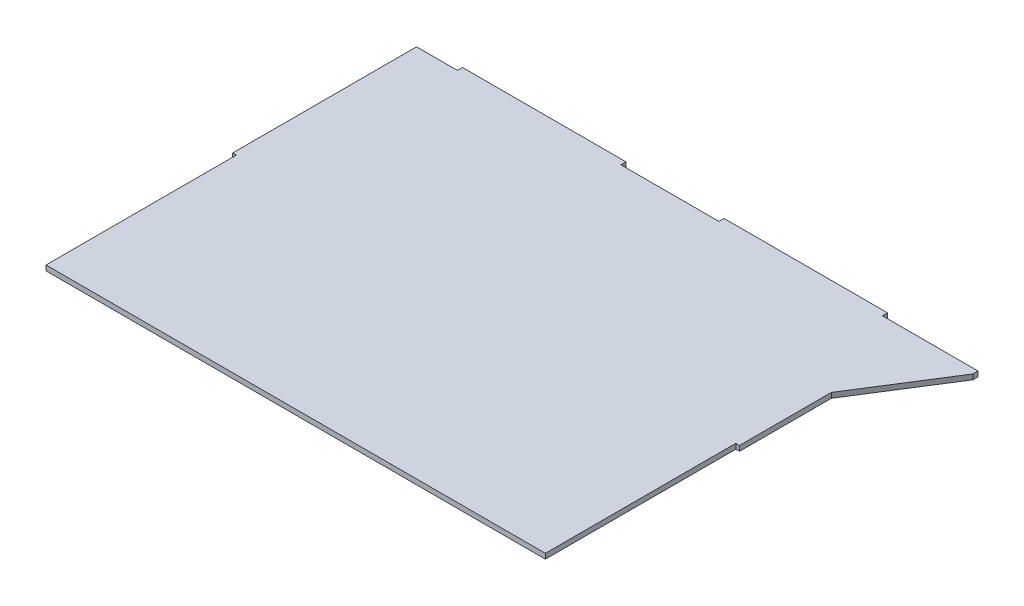
SolidWorks part; units mm, degrees
material "6061-T6 (SS)"
ref_plane "X-Y Datum" through (0, 0, 0) normal (0, 0, 1) x (1, 0, 0)
ref_plane "X-Z Datum" through (0, 0, 0) normal (0, 1, 0) x (1, 0, 0)
ref_plane "Y-Z Datum" through (0, 0, 0) normal (1, 0, 0) x (0, 0, -1)
sketch "Sketch1" plane through (0, 0, 0) normal (0, 0, 1) x (1, 0, 0)
  line L1 (-157.4823, -1.5875) -> (157.4823, -1.5875)
  line L2 (-157.4823, -1.5875) -> (-157.4823, 1.5875)
  line L3 (-157.4823, 1.5875) -> (157.4823, 1.5875)
  line L4 (157.4823, -1.5875) -> (157.4823, 1.5875)
  line L5 (-157.4823, -1.5875) -> (157.4823, 1.5875) construction
  line L6 (-157.4823, 1.5875) -> (157.4823, -1.5875) construction
  point P0 (0, 0)
  dimension "D1" = 314.9646
  dimension "D2" = 3.175
extrude "Boss-Extrude1" add sketch "Sketch1" along normal blind 235.775
sketch "Sketch3" plane through (0, 0, 0) normal (0, 0, -1) x (-1, 0, 0)
  line L0 (-157.4823, 0) -> (-81.2823, 0) construction
  line L1 (-157.4823, -1.5875) -> (-157.4823, 1.5875) construction
  line L2 (-157.4823, 1.5875) -> (157.4823, 1.5875) construction
  line L3 (-132.0823, -1.5875) -> (-30.4823, -1.5875)
  line L4 (-132.0823, -1.5875) -> (-132.0823, 1.5875)
  line L5 (-132.0823, 1.5875) -> (-30.4823, 1.5875)
  line L6 (-30.4823, -1.5875) -> (-30.4823, 1.5875)
  line L7 (-132.0823, -1.5875) -> (-30.4823, 1.5875) construction
  line L8 (-132.0823, 1.5875) -> (-30.4823, -1.5875) construction
  line L14 (-157.4823, 1.5875) -> (-132.0823, 1.5875)
  line L15 (-157.4823, 1.5875) -> (-157.4823, -1.5875)
  line L16 (-157.4823, -1.5875) -> (-132.0823, -1.5875)
  line L17 (-132.0823, 1.5875) -> (-132.0823, -1.5875)
  line L19 (-30.4823, 1.5875) -> (-30.4823, -1.5875)
  line L20 (0, 43.0151) -> (0, -43.0151) construction
  line L21 (30.4823, -1.5875) -> (30.4823, 1.5875)
  line L22 (132.0823, -1.5875) -> (132.0823, 1.5875)
  line L23 (132.0823, 1.5875) -> (30.4823, 1.5875)
  line L24 (132.0823, -1.5875) -> (30.4823, 1.5875) construction
  line L25 (132.0823, -1.5875) -> (30.4823, -1.5875)
  line L26 (132.0823, 1.5875) -> (30.4823, -1.5875) construction
  line M2 (-157.4823, 1.5875) -> (-157.4823, -1.5875)
  line M3 (-157.4823, -1.5875) -> (157.4823, -1.5875)
  line M4 (157.4823, -1.5875) -> (157.4823, 1.5875)
  line M5 (157.4823, 1.5875) -> (-157.4823, 1.5875)
  dimension "D1" = 76.2
  dimension "D2" = 101.6
extrude "Cut-Extrude1" cut sketch "Sketch3" against normal blind 3.175 contours L4 M3 M5 M2 | L6 M3 M5 | M3 M4 M5 region at (144.7823, 0, 0) region at (0, 0, 0) region at (-144.7823, 0, 0)
sketch "Sketch5" plane through (0, 1.5875, 0) normal (0, 1, 0) x (1, 0, 0)
  line L1 (-157.4823, -235.775) -> (-155.1963, -235.775)
  line L3 (-157.4823, -235.775) -> (-157.4823, -117.411)
  line L5 (-157.4823, -117.411) -> (-155.1963, -117.411)
  line L6 (-155.1963, -235.775) -> (-155.1963, -117.411)
  line M11 (-157.4823, -3.175) -> (-157.4823, -235.775)
  line M12 (-157.4823, -235.775) -> (157.4823, -235.775)
  dimension "D1" = 118.364
  dimension "D2" = 2.286
extrude "Cut-Extrude2" cut sketch "Sketch5" against normal blind 3.175 and the other way through all contours M12 M11 region at (-156.3393, 1.5875, 176.593)
mirror "Mirror1" about plane through (0, 0, 0) normal (1, 0, 0) of "Cut-Extrude2"
sketch "Sketch6" plane through (0, 1.5875, 0) normal (0, 1, 0) x (1, 0, 0)
  line L6 (-157.4823, -215.455) -> (-81.2823, -215.455)
  line L7 (-157.4823, -215.455) -> (-157.4823, -235.775)
  line L8 (-157.4823, -235.775) -> (-81.2823, -235.775)
  line L9 (-81.2823, -215.455) -> (-81.2823, -235.775)
  line L10 (155.1963, -235.775) -> (-155.1963, -235.775) construction
  line L11 (-157.4823, -117.411) -> (-157.4823, -3.175) construction
  line L13 (155.1963, -235.775) -> (-81.2823, -235.775)
  line L14 (155.1963, -235.775) -> (155.1963, -215.455)
  line L15 (155.1963, -215.455) -> (-81.2823, -215.455)
  line L16 (-81.2823, -235.775) -> (-81.2823, -215.455)
  dimension "D1" = 76.2
  dimension "D2" = 20.32
extrude "Cut-Extrude4" [suppressed] cut sketch "Sketch6" against normal through all
sketch "Sketch7" [suppressed] plane through (0, 1.5875, 0) normal (0, 1, 0) x (1, 0, 0)
  line L1 (-81.2823, -215.455) -> (155.1963, -215.455)
  line L2 (-81.2823, -215.455) -> (-81.2823, -235.775)
  line L3 (-81.2823, -235.775) -> (155.1963, -235.775)
  line L4 (155.1963, -215.455) -> (155.1963, -235.775)
extrude "Cut-Extrude5" [suppressed] cut sketch "Sketch7" against normal through all
sketch "Sketch8" [suppressed] plane through (0, 1.5875, 0) normal (0, 1, 0) x (1, 0, 0)
  line L0 (155.1963, -235.775) -> (-155.1963, -235.775) construction
  line L1 (157.4823, -215.455) -> (81.2823, -215.455)
  line L2 (157.4823, -215.455) -> (157.4823, -235.775)
  line L3 (157.4823, -235.775) -> (81.2823, -235.775)
  line L4 (81.2823, -215.455) -> (81.2823, -235.775)
  line L5 (157.4823, -117.411) -> (157.4823, -3.175) construction
  dimension "D1" = 20.32
  dimension "D2" = 76.2
extrude "Cut-Extrude6" [suppressed] cut sketch "Sketch8" against normal through all
sketch "Sketch9" [suppressed] plane through (0, 0, 215.455) normal (0, 0, 1) x (1, 0, 0)
  line L4 (155.1963, 1.5875) -> (-155.1963, 1.5875)
  line L5 (-155.1963, 1.5875) -> (-155.1963, -1.5875)
  line L6 (-155.1963, -1.5875) -> (155.1963, -1.5875)
  line L7 (155.1963, -1.5875) -> (155.1963, 1.5875)
  line L8 (155.1963, 1.5875) -> (-155.1963, 1.5875)
  line L9 (-155.1963, 1.5875) -> (-155.1963, -1.5875)
  line L10 (-155.1963, -1.5875) -> (155.1963, -1.5875)
  line L11 (155.1963, -1.5875) -> (155.1963, 1.5875)
  dimension "D1" = 0
extrude "Cut-Extrude7" [suppressed] cut sketch "Sketch9" against normal blind 11.68
sketch "Sketch10" plane through (0, 1.5875, 0) normal (0, 1, 0) x (1, 0, 0)
  line L0 (157.4823, -3.175) -> (191.5183, -3.175)
  line L2 (157.4823, -117.411) -> (157.4823, -3.175) construction
  line L3 (157.4823, -60.293) -> (157.4823, -3.175)
  line L4 (191.5183, -3.175) -> (191.5183, -6.35)
  line L5 (157.4823, -60.293) -> (191.5183, -6.35)
  dimension "D1" = 34.036
extrude "Boss-Extrude2" add sketch "Sketch10" against normal blind 3.175
mirror "Mirror2" [suppressed] about plane through (0, 0, 0) normal (1, 0, 0)
